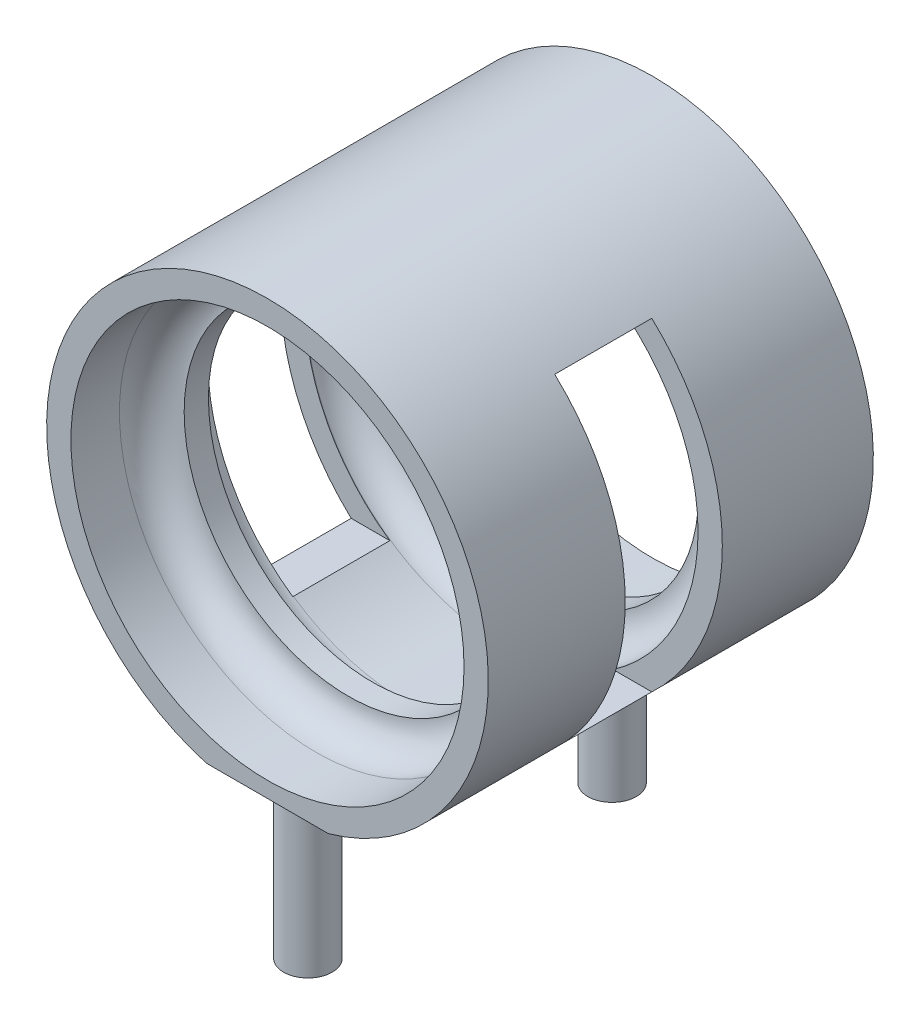
SolidWorks part; units mm, degrees
ref_plane "Front Plane" through (0, 0, 0) normal (0, 0, 1) x (1, 0, 0)
ref_plane "Top Plane" through (0, 0, 0) normal (0, 1, 0) x (1, 0, 0)
ref_plane "Right Plane" through (0, 0, 0) normal (1, 0, 0) x (0, 0, -1)
sketch "Sketch1" plane through (0, 0, 0) normal (0, 0, 1) x (1, 0, 0)
  line L0 (-3.7667, -13.12) -> (3.7667, -13.12)
  line L1 (0, -55) -> (0, 55) construction
  line L2 (0, -13.65) -> (6.7961, -13.65) construction
  circle A0 centre (0, 0) radius 12.15
  circle A1 centre (0, 0) radius 13.65
  point P6 (0, -13.12)
  dimension "D1" = 24.3
  dimension "D2" = 27.3
  dimension "D3" = 0.53
extrude "Boss-Extrude1" add sketch "Sketch1" along normal blind 23.8 contours L0 A1 A0 region at (-7.983, 10.5973, 0)
sketch "Sketch2" plane through (0, 0, 23.8) normal (0, 0, 1) x (1, 0, 0)
  circle A1 centre (0, 0) radius 12.15
  circle A2 centre (0, 0) radius 10.15
  circle A3 centre (0, 0) radius 10.15
  dimension "D1" = 2
extrude "Boss-Extrude2" add sketch "Sketch2" against normal blind 1.5 from offset 5 offset against normal yes
extrude "Boss-Extrude3" add sketch "Sketch2<2>" along normal blind 1.5 from offset 18 offset against normal yes
sketch "Sketch2<2>" plane through (0, 0, 23.8) normal (0, 0, 1) x (1, 0, 0) same geometry as "Sketch2"
sketch "Sketch4" plane through (0, 0, 0) normal (1, 0, 0) x (0, 0, -1)
  line L0 (13.09, 0) -> (-13.09, 0) construction
  line L1 (-15.3358, -10) -> (-9.3358, -10)
  line L2 (-15.3358, -10) -> (-15.3358, 10)
  line L3 (-15.3358, 10) -> (-9.3358, 10)
  line L4 (-9.3358, -10) -> (-9.3358, 10)
  line L5 (-15.3358, -10) -> (-9.3358, 10) construction
  line L6 (-15.3358, 10) -> (-9.3358, -10) construction
  point P0 (-12.3358, 0)
  dimension "D1" = 20
  dimension "D2" = 6
extrude "Cut-Extrude1" cut sketch "Sketch4" against normal through all both and the other way through all
sketch "Sketch5" plane through (0, -13.12, 0) normal (0, -1, 0) x (1, 0, 0)
  line L0 (0, 23.8) -> (0, 0) construction
  line L1 (-3.7667, 23.8) -> (3.7667, 23.8) construction
  line L2 (0, 21.3) -> (0, 2.5) construction
  circle A0 centre (0, 21.3) radius 1.5
  circle A1 centre (0, 2.5) radius 1.5
  point P7 (0, 11.9)
  point P8 (0, 11.9)
  dimension "D2" = 3
  dimension "D3" = 3
  dimension "D1" = 18.8
extrude "Boss-Extrude4" add sketch "Sketch5" along normal blind 9.8
fillet "Fillet1" radius 2 4 edges at (12.15, 0, 5.8) (12.15, 0, 7.3) (12.15, 0, 17.3) (12.15, 0, 18.8)
